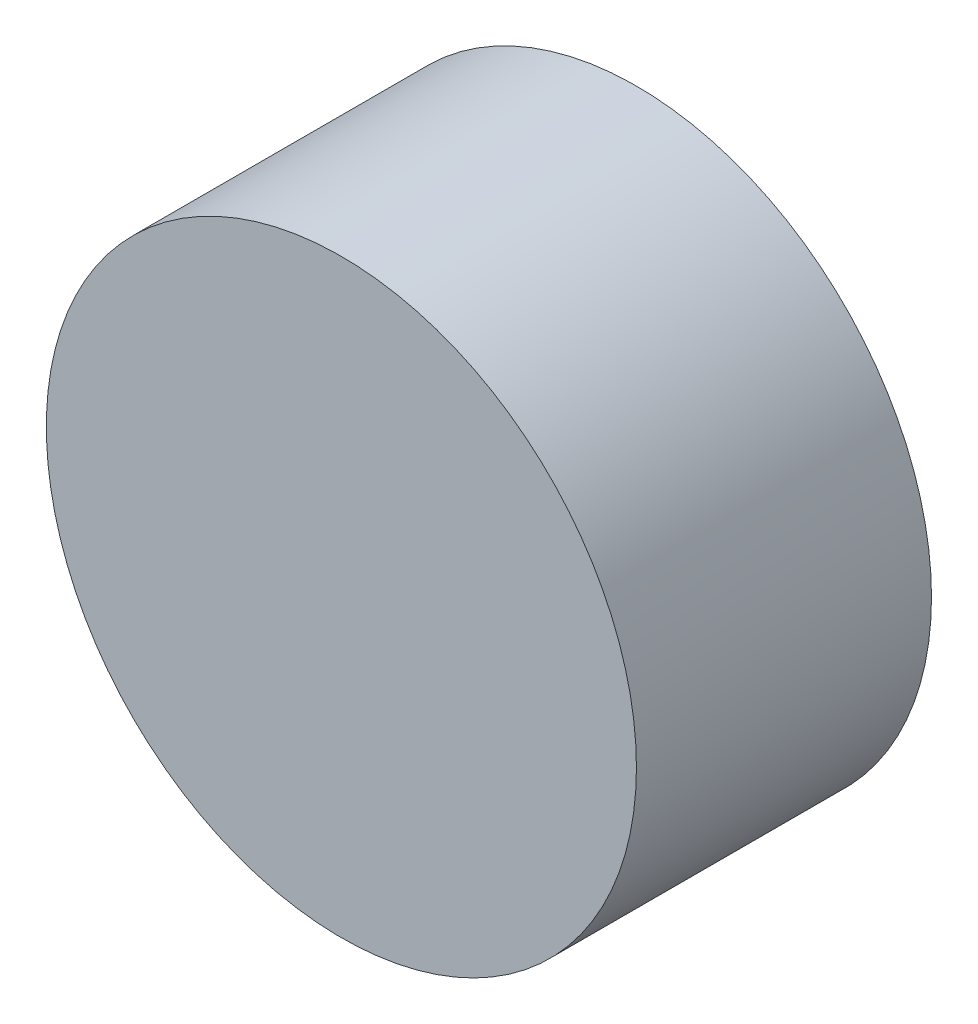
SolidWorks part; units mm, degrees
ref_plane "Ebene vorne" through (0, 0, 0) normal (0, 0, 1) x (1, 0, 0)
ref_plane "Ebene oben" through (0, 0, 0) normal (0, 1, 0) x (1, 0, 0)
ref_plane "Ebene rechts" through (0, 0, 0) normal (1, 0, 0) x (0, 0, -1)
sketch "Skizze1" plane through (0, 0, 0) normal (0, 0, 1) x (1, 0, 0)
  circle A0 centre (0, 0) radius 10
  dimension "D1" = 20
extrude "Aufsatz-Linear austragen1" add sketch "Skizze1" along normal blind 10
sketch "Skizze2" plane through (0, 0, 0) normal (0, 0, -1) x (-1, 0, 0)
  line L0 (1, 9.9499) -> (1, -10.3733)
  line L1 (-10.5928, -1) -> (11.0165, -1)
  circle A0 centre (0, 0) radius 10 construction
  point P6 (1, -1)
  dimension "D1" = 1
  dimension "D2" = 1
ref_axis "Achse1" through (0, 0, 10) along (0, 0, -1)
ref_plane "Ebene1" through (0, 0, 0) normal (1, 0, 0) x (0, 0, -1)
